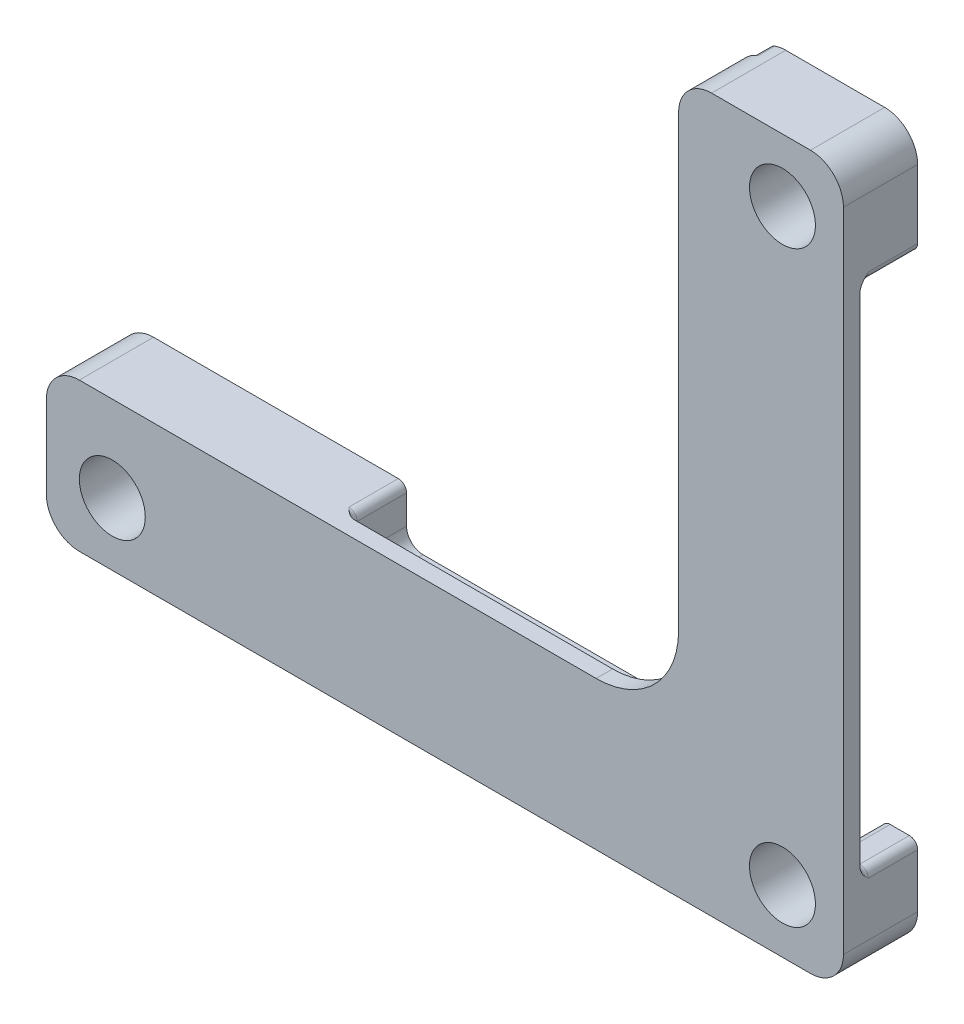
SolidWorks part; units mm, degrees
material "PLA"
ref_plane "Alzado" through (0, 0, 0) normal (0, 0, 1) x (1, 0, 0)
ref_plane "Planta" through (0, 0, 0) normal (0, 1, 0) x (1, 0, 0)
ref_plane "Vista lateral" through (0, 0, 0) normal (1, 0, 0) x (0, 0, -1)
sketch "Sketch1" plane through (0, 0, 0) normal (0, 0, 1) x (1, 0, 0)
  line L0 (44.65, 39.45) -> (44.65, 3.8) construction
  line L1 (0, 0) -> (48.35, 0)
  line L2 (0, 0) -> (0, 43.25)
  line L3 (0, 43.25) -> (48.35, 43.25)
  line L4 (48.35, 0) -> (48.35, 43.25)
  line L5 (4, 39.45) -> (44.65, 39.45) construction
  line L6 (4, 39.45) -> (4, 3.8) construction
  line L7 (4, 3.8) -> (44.65, 3.8) construction
  line L8 (44.65, 21.625) -> (48.35, 21.625) construction
  circle A0 centre (44.65, 39.45) radius 2
  circle A1 centre (44.65, 3.8) radius 2
  circle A2 centre (4, 3.8) radius 2
  dimension "D3" = 4
  dimension "D4" = 3.7
  dimension "D1" = 48.35
  dimension "D2" = 43.25
  dimension "D7" = 40.65
  dimension "D9" = 35.65
extrude "Boss-Extrude2" add sketch "Sketch1" along normal blind 4.5
sketch "Croquis1" plane through (0, 0, 4.5) normal (0, 0, 1) x (1, 0, 0)
  line L0 (48.35, 0) -> (48.35, 43.25) construction
  line L1 (0, 43.25) -> (38.35, 43.25)
  line L2 (0, 43.25) -> (0, 9)
  line L3 (0, 9) -> (38.35, 9)
  line L4 (38.35, 43.25) -> (38.35, 9)
  line L5 (0, 0) -> (48.35, 0) construction
  dimension "D1" = 10
  dimension "D2" = 9
extrude "Cortar-Extruir1" cut sketch "Croquis1" against normal through all
sketch "Croquis2" plane through (0, 0, 0) normal (0, 0, -1) x (-1, 0, 0)
  line L0 (-48.35, 43.25) -> (-38.35, 43.25) construction
  line L1 (-48.35, 36.6) -> (-17.35, 36.6)
  line L2 (-48.35, 36.6) -> (-48.35, 5.75)
  line L3 (-48.35, 5.75) -> (-17.35, 5.75)
  line L4 (-17.35, 36.6) -> (-17.35, 5.75)
  line L5 (0, 0) -> (-48.35, 0) construction
  line L6 (-48.35, 0) -> (-48.35, 43.25) construction
  dimension "D1" = 6.65
  dimension "D2" = 5.75
  dimension "D3" = 31
extrude "Cortar-Extruir2" cut sketch "Croquis2" against normal offset from surface (3.5 mm away) 1 up to face at (46.65, 3.8, 4.5)
sketch "Croquis3" plane through (0, 0, 0) normal (0, 0, -1) x (-1, 0, 0)
  line L0 (-38.35, 36.6) -> (-38.35, 43.25) construction
  line L1 (-38.35, 43.25) -> (-39.35, 43.25)
  line L2 (-38.35, 43.25) -> (-38.35, 36.6)
  line L3 (-38.35, 36.6) -> (-39.35, 36.6)
  line L4 (-39.35, 43.25) -> (-39.35, 36.6)
  line L5 (-48.35, 43.25) -> (-38.35, 43.25) construction
  line L6 (-38.35, 36.6) -> (-48.35, 36.6) construction
  dimension "D1" = 1
extrude "Cortar-Extruir3" cut sketch "Croquis3" against normal blind 1
fillet "Redondeo1" radius 2 5 edges at (0, 0, 2.25) (48.35, 43.25, 2.25) (48.35, 0, 2.25) (0, 9, 2.25) (38.35, 43.25, 2.75)
fillet "Redondeo2" radius 5 1 edges at (38.35, 9, 4)
fillet "Redondeo3" radius 1 1 edges at (17.35, 5.75, 1.75)
fillet "Redondeo7" radius 0.5 6 edges at (45.0944, 5.75, 1.75) (44.2056, 5.75, 1.75) (17.35, 9, 1.75) (48.35, 5.75, 1.75) (48.35, 36.6, 1.75) (38.35, 36.6, 2.25)
fillet "Redondeo8" radius 0.5 2 edges at (39.35, 36.6, 0.5) (39.35, 42.9821, 0.5)
fillet "Redondeo5" radius 0.5 11 edges at (17.35, 7.625, 3.5) (17.6429, 6.0429, 3.5) (43.35, 36.6, 3.5) (30.4817, 5.75, 3.5) (48.2036, 36.7464, 3.5) (38.4964, 36.7464, 3.5) (17.2036, 8.8536, 3.5) (43.0579, 5.4791, 3.5) (46.2421, 5.4791, 3.5) (48.2036, 5.6036, 3.5) (47.2683, 5.75, 3.5)
